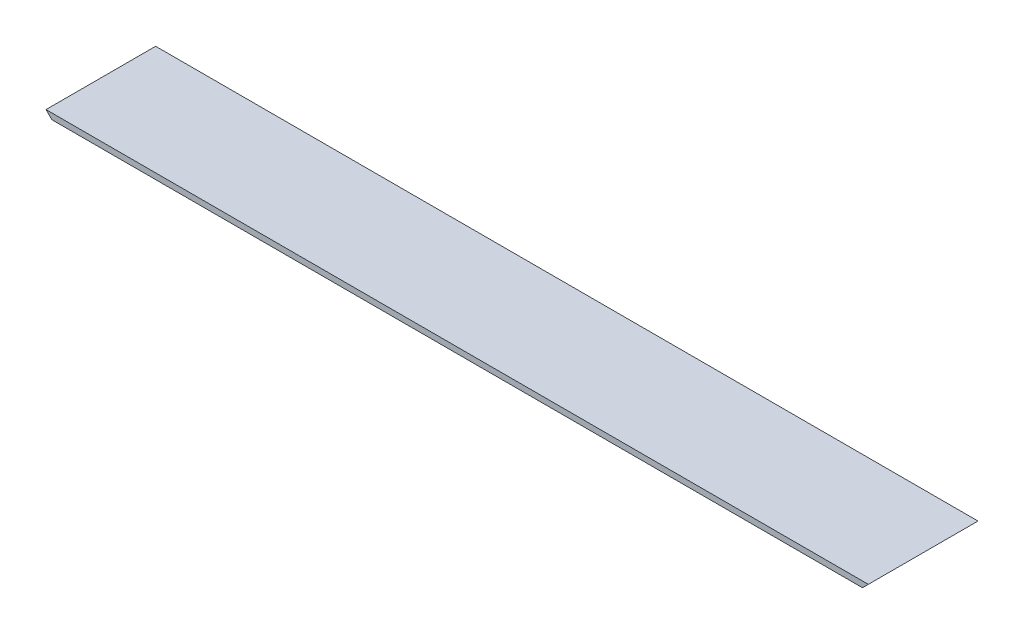
SolidWorks part; units mm, degrees
ref_plane "Front Plane" through (0, 0, 0) normal (0, 0, 1) x (1, 0, 0)
ref_plane "Top Plane" through (0, 0, 0) normal (0, 1, 0) x (1, 0, 0)
ref_plane "Right Plane" through (0, 0, 0) normal (1, 0, 0) x (0, 0, -1)
sketch "Sketch1" plane through (0, 0, 0) normal (0, 1, 0) x (1, 0, 0)
  line L1 (1333.5, 177.8) -> (-1333.5, 177.8)
  line L2 (1333.5, 177.8) -> (1333.5, -177.8)
  line L3 (1333.5, -177.8) -> (-1333.5, -177.8)
  line L4 (-1333.5, 177.8) -> (-1333.5, -177.8)
  line L5 (1333.5, 177.8) -> (-1333.5, -177.8) construction
  line L6 (1333.5, -177.8) -> (-1333.5, 177.8) construction
  point P0 (0, 0)
  dimension "D1" = 2667
  dimension "D2" = 355.6
extrude "Boss-Extrude1" add sketch "Sketch1" along normal blind 19.05 contours L4 L3 L2 L1
chamfer "Chamfer1" distance 19.05 angle 45 2 edges at (1333.5, 0, 0) (-1333.5, 0, 0)
